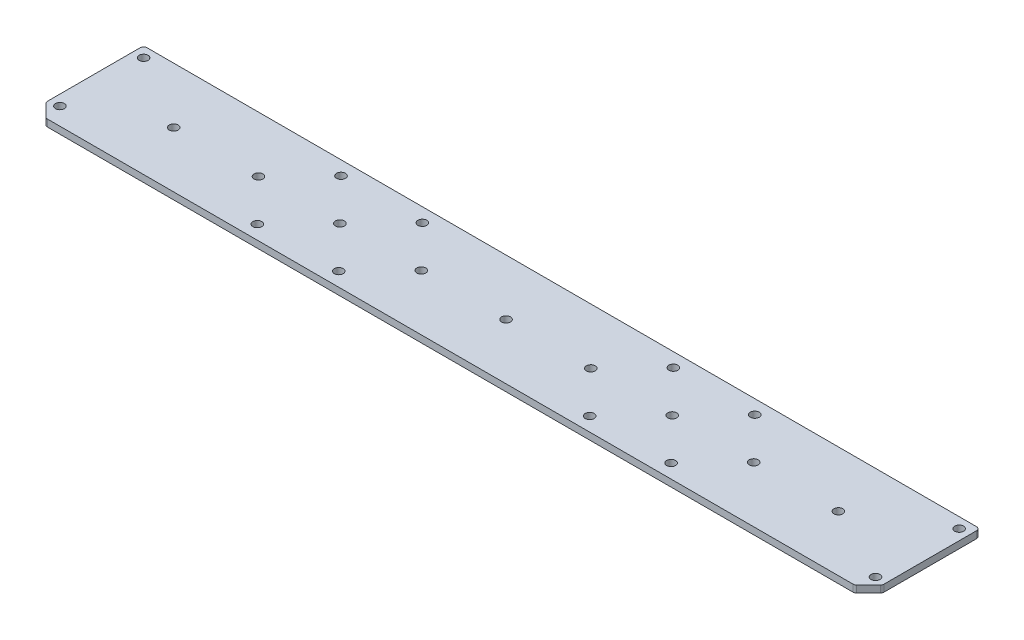
SolidWorks part; units mm, degrees
ref_plane "Front Plane" through (0, 0, 0) normal (0, 0, 1) x (1, 0, 0)
ref_plane "Top Plane" through (0, 0, 0) normal (0, 1, 0) x (1, 0, 0)
ref_plane "Right Plane" through (0, 0, 0) normal (1, 0, 0) x (0, 0, -1)
sketch "Sketch2" plane through (0, 0, 0) normal (0, 1, 0) x (1, 0, 0)
  line L0 (0, 7.0076) -> (0, 50.8)
  line L1 (0, 50.8) -> (381, 50.8)
  line L2 (381, 50.8) -> (381, 7.0076)
  line L3 (373.9924, 0) -> (7.0076, 0)
  line L4 (5.885, 0.465) -> (0.465, 5.885) construction
  line L5 (5.885, 0.465) -> (0.465, 5.885)
  line L6 (375.115, 0.465) -> (380.535, 5.885) construction
  line L7 (375.115, 0.465) -> (380.535, 5.885)
  line L8 (336.5758, 50.8) -> (379.4125, 50.8) construction
  arc A0 (5.885, 0.465) -> (7.0076, 0) centre (7.0076, 1.5875) ccw construction
  arc A1 (0, 7.0076) -> (0.465, 5.885) centre (1.5875, 7.0076) ccw construction
  arc A2 (5.885, 0.465) -> (7.0076, 0) centre (7.0076, 1.5875) ccw
  arc A3 (0, 7.0076) -> (0.465, 5.885) centre (1.5875, 7.0076) ccw
  arc A4 (373.9924, 0) -> (375.115, 0.465) centre (373.9924, 1.5875) ccw construction
  arc A6 (373.9924, 0) -> (375.115, 0.465) centre (373.9924, 1.5875) ccw
  arc A8 (380.535, 5.885) -> (381, 7.0076) centre (379.4125, 7.0076) ccw construction
  arc A9 (380.535, 5.885) -> (381, 7.0076) centre (379.4125, 7.0076) ccw
extrude "Boss-Extrude1" add sketch "Sketch2" along normal blind 3.175
sketch "Sketch3" plane through (0, 0, 0) normal (0, 1, 0) x (1, 0, 0)
  circle A25 centre (4.7625, 7.9375) radius 2.032 construction
  circle A31 centre (4.7625, 46.0375) radius 2.032 construction
  circle A63 centre (376.2375, 7.9375) radius 2.032 construction
  circle A64 centre (376.2375, 46.0375) radius 2.032 construction
  circle A67 centre (4.7625, 7.9375) radius 2.032
  circle A68 centre (4.7625, 46.0375) radius 2.032
  circle A72 centre (376.2375, 7.9375) radius 2.032
  circle A73 centre (376.2375, 46.0375) radius 2.032
  circle A123 centre (341.884, 25.4) radius 2.032 construction
  circle A124 centre (247.65, 44.45) radius 2.032 construction
  circle A125 centre (284.734, 44.45) radius 2.032 construction
  circle A128 centre (247.65, 6.35) radius 2.032 construction
  circle A129 centre (284.734, 6.35) radius 2.032 construction
  circle A132 centre (190.5, 25.4) radius 2.032 construction
  circle A134 centre (170.434, 6.35) radius 2.032 construction
  circle A135 centre (133.35, 44.45) radius 2.032 construction
  circle A136 centre (96.266, 44.45) radius 2.032 construction
  circle A137 centre (96.266, 6.35) radius 2.032 construction
  circle A140 centre (77.724, 25.4) radius 2.032 construction
  circle A141 centre (39.116, 25.4) radius 2.032 construction
  circle A142 centre (341.884, 25.4) radius 2.032
  circle A143 centre (247.65, 44.45) radius 2.032
  circle A144 centre (284.734, 44.45) radius 2.032
  circle A147 centre (247.65, 6.35) radius 2.032
  circle A148 centre (284.734, 6.35) radius 2.032
  circle A151 centre (190.5, 25.4) radius 2.032
  circle A154 centre (133.35, 44.45) radius 2.032
  circle A155 centre (96.266, 44.45) radius 2.032
  circle A156 centre (96.266, 6.35) radius 2.032
  circle A159 centre (77.724, 25.4) radius 2.032
  circle A160 centre (39.116, 25.4) radius 2.032
  circle A161 centre (151.892, 25.4) radius 2.032
  circle A162 centre (229.108, 25.4) radius 2.032
  circle A163 centre (266.192, 25.4) radius 2.032
  circle A164 centre (303.276, 25.4) radius 2.032
  circle A165 centre (151.892, 25.4) radius 2.3813 construction
  circle A166 centre (229.108, 25.4) radius 2.3813 construction
  circle A167 centre (266.192, 25.4) radius 2.3813 construction
  circle A168 centre (303.276, 25.4) radius 2.3813 construction
  circle A169 centre (133.35, 6.35) radius 2.032
  circle A170 centre (114.808, 25.4) radius 2.032 construction
  circle A171 centre (114.808, 25.4) radius 2.032
extrude "Cut-Extrude1" cut sketch "Sketch3" along normal through all
fillet "Fillet1" radius 1.5875 2 edges at (0, 1.5875, -50.8) (381, 1.5875, -50.8)
